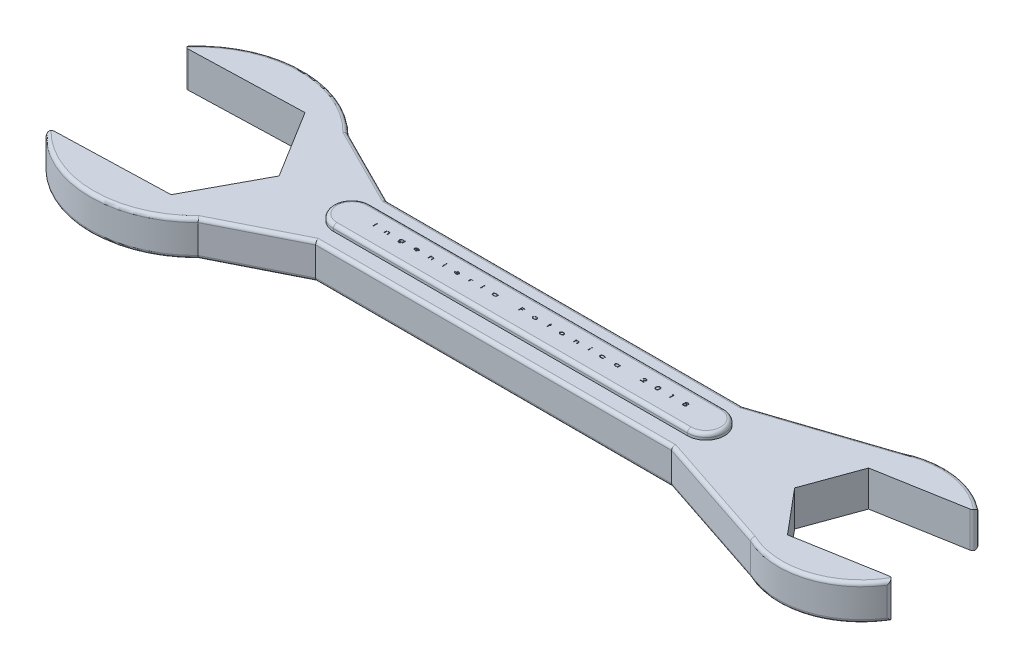
SolidWorks part; units mm, degrees
ref_plane "Alzado" through (0, 0, 0) normal (0, 0, 1) x (1, 0, 0)
ref_plane "Planta" through (0, 0, 0) normal (0, 1, 0) x (1, 0, 0)
ref_plane "Vista lateral" through (0, 0, 0) normal (1, 0, 0) x (0, 0, -1)
sketch "Croquis1" plane through (0, 0, 0) normal (0, 1, 0) x (1, 0, 0)
  line L0 (150, 30) -> (249.7385, 63.1208)
  line L1 (-150, -30) -> (150, -30)
  line L3 (-150, 30) -> (150, 30)
  line L7 (150, -30) -> (249.7385, -63.1208)
  line L8 (-150, -30) -> (-215.8458, -63.1208)
  line L10 (-150, 30) -> (-215.8458, 63.1208)
  arc A0 (249.7385, -63.1208) -> (249.7385, 63.1208) centre (280, 0) ccw
  arc A1 (-215.8458, 63.1208) -> (-215.8458, -63.1208) centre (-280, 0) ccw
  point P0 (0, 0)
  dimension "D1" = 280
  dimension "D2" = 280
extrude "Saliente-Extruir3" add sketch "Croquis1" along normal blind 30 contours A0 L0 L3 L10 A1 L8 L1 L7
sketch "Croquis9" plane through (0, 0, 0) normal (0, 1, 0) x (1, 0, 0)
  line L1 (-248.1651, 59.1914) -> (-315.3438, 57.1655)
  line L4 (-311.8349, -59.1914) -> (-244.6562, -57.1655)
  line L5 (-244.6562, -57.1655) -> (-212.8213, 2.0259)
  line L6 (-212.8213, 2.0259) -> (-248.1651, 59.1914)
  line L8 (296.6324, 45.697) -> (248.7414, 37.2526)
  line L9 (248.7414, 37.2526) -> (232.109, -8.4445)
  line L10 (232.109, -8.4445) -> (263.3676, -45.697)
  line L11 (263.3676, -45.697) -> (311.2586, -37.2526)
  line L13 (296.6324, 45.697) -> (385.6188, 61.3878)
  line L14 (311.2586, -37.2526) -> (400.245, -21.5619)
  line L15 (385.6188, 61.3878) -> (400.245, -21.5619)
  line L17 (-315.3438, 57.1655) -> (-416.8929, 54.1032)
  line L18 (-311.8349, -59.1914) -> (-413.384, -62.2538)
  line L19 (-416.8929, 54.1032) -> (-413.384, -62.2538)
  line L20 (-315.3438, 57.1655) -> (-331.2613, 27.5698) [skipped]
  line L21 (-329.5068, -30.6086) -> (-311.8349, -59.1914) [skipped]
  line L23 (311.2586, -37.2526) -> (319.5748, -14.4041) [skipped]
  line L24 (312.2617, 27.0708) -> (296.6324, 45.697) [skipped]
extrude "Cortar-Extruir4" cut sketch "Croquis9" along normal blind 60
sketch "Croquis10" plane through (0, 0, 0) normal (0, 1, 0) x (1, 0, 0)
  line L0 (-149.4852, 0) -> (148.9785, 0) construction
  line L1 (-149.4852, 15.5385) -> (148.9785, 15.5385)
  line L2 (-149.4852, -15.5385) -> (148.9785, -15.5385)
  arc A0 (-149.4852, 15.5385) -> (-149.4852, -15.5385) centre (-149.4852, 0) ccw
  arc A1 (148.9785, -15.5385) -> (148.9785, 15.5385) centre (148.9785, 0) ccw
  point P3 (-0.2533, 0)
extrude "Saliente-Extruir4" add sketch "Croquis10" along normal blind 35
ref_plane "Plano1" through (0, 35, 0) normal (0, 1, 0) x (1, 0, 0)
sketch "Croquis13" plane through (0, 35, 0) normal (0, 1, 0) x (1, 0, 0)
  line L0 (-165.0237, 0) -> (164.517, 0) construction
  arc A0 (-149.4852, 15.5385) -> (-149.4852, -15.5385) centre (-149.4852, 0) ccw construction
  arc A1 (148.9785, -15.5385) -> (148.9785, 15.5385) centre (148.9785, 0) ccw construction
  text T0 "Ingenieria Fotonica 2018" font "Century Gothic" height 3.5
extrude "Cortar-Extruir5" cut sketch "Croquis13" against normal blind 5
fillet "Redondeo3" radius 3 28 edges at (-165.0237, 35, 0) (-0.2533, 35, -15.5385) (164.517, 35, 0) (-346.8597, 15, 60.2476) (0, 0, 30) (302.4421, 0, 66.305) (199.8692, 0, 46.5604) (290.5874, 0, -69.1947) (199.8692, 0, -46.5604) (-284.6846, 0, -89.878) (-182.9229, 0, -46.5604) (-182.9229, 0, 46.5604) (342.3775, 15, 31.7655) (327.7513, 15, -51.1841) (290.5874, 30, -69.1947) (199.8692, 30, -46.5604) (0, 30, -30) (302.4421, 30, 66.305) (-0.2533, 35, 15.5385) (199.8692, 30, 46.5604) (-182.9229, 30, 46.5604) (-281.9733, 0, 89.9784) (-281.9733, 30, 89.9784) (-350.3686, 15, -56.1093) (-284.6846, 30, -89.878) (-182.9229, 30, -46.5604) (0, 0, -30) (0, 30, 30)
